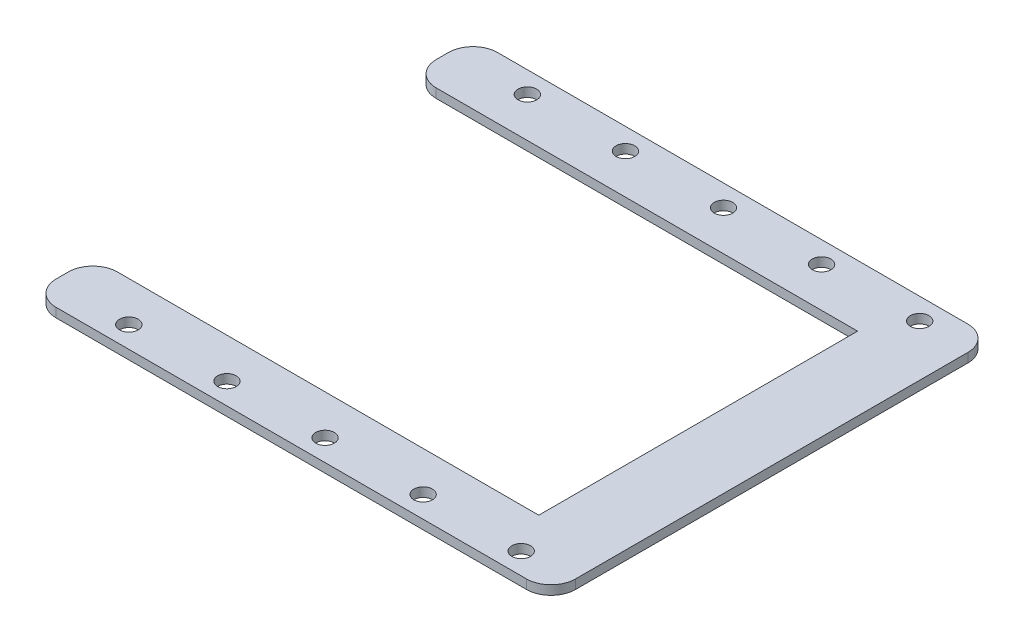
SolidWorks part; units mm, degrees
ref_plane "Front Plane" through (0, 0, 0) normal (0, 0, 1) x (1, 0, 0)
ref_plane "Top Plane" through (0, 0, 0) normal (0, 1, 0) x (1, 0, 0)
ref_plane "Right Plane" through (0, 0, 0) normal (1, 0, 0) x (0, 0, -1)
sketch "Sketch1" plane through (0, 0, 0) normal (0, 1, 0) x (1, 0, 0)
  line L0 (-76.7804, -46.0375) -> (76.7804, -46.0375) construction
  line L1 (76.7804, -57.15) -> (-76.7804, -57.15)
  line L2 (76.7804, -57.15) -> (76.7804, 57.15)
  line L3 (76.7804, 57.15) -> (-76.7804, 57.15)
  line L4 (-76.7804, -57.15) -> (-76.7804, 57.15)
  line L5 (76.7804, -57.15) -> (-76.7804, 57.15) construction
  line L6 (76.7804, 57.15) -> (-76.7804, -57.15) construction
  line L7 (57.7304, -41.275) -> (-63.1045, -41.275)
  line L8 (57.7304, -41.275) -> (57.7304, 15.875)
  line L9 (21.3279, 41.275) -> (57.7304, 41.275)
  line L10 (-63.1045, -41.275) -> (-63.1045, 41.275)
  line L11 (-76.7804, 0) -> (76.7804, 0) construction
  line L12 (21.3279, 41.275) -> (-63.1045, 41.275)
  line L13 (-76.7804, -51.5937) -> (76.7804, -51.5937) construction
  line L14 (63.5, -51.5938) -> (76.7804, -46.0375) construction
  line L15 (-63.5, -51.5938) -> (-76.7804, -46.0375) construction
  line L16 (57.7304, 41.275) -> (57.7304, 15.875)
  circle A0 centre (-63.5, -51.5938) radius 2.413
  circle A1 centre (-38.1, -51.5938) radius 2.413
  circle A2 centre (-12.7, -51.5938) radius 2.413
  circle A3 centre (12.7, -51.5938) radius 2.413
  circle A4 centre (38.1, -51.5938) radius 2.413
  circle A5 centre (63.5, -51.5938) radius 2.413
  circle A6 centre (63.5, 51.5938) radius 2.413
  circle A7 centre (38.1, 51.5938) radius 2.413
  circle A8 centre (12.7, 51.5938) radius 2.413
  circle A9 centre (-12.7, 51.5937) radius 2.413
  circle A10 centre (-38.1, 51.5937) radius 2.413
  circle A11 centre (-63.5, 51.5937) radius 2.413
  point P0 (0, 0)
  point P6 (0, 0)
  dimension "D6" = 4.826
  dimension "D8" = 25.4
  dimension "D1" = 114.3
  dimension "D2" = 153.5608
  dimension "D3" = 15.875
  dimension "D4" = 11.1125
  dimension "D5" = 5.5562
  dimension "D10" = 13.6759
  dimension "D11" = 19.05
  dimension "D7" = 6
base flange "Base-Flange1" sketch "Sketch1" thickness 2.3813 reverse thickness direction no parameters "D1"=2.3813
fillet "Fillet1" radius 6.35 4 edges at (-76.7804, -1.1906, 57.15) (-76.7804, -1.1906, -57.15) (76.7804, -1.1906, -57.15) (76.7804, -1.1906, 57.15)
sketch "Sketch7" plane through (0, -2.3813, 0) normal (0, -1, 0) x (-1, 0, 0)
  line L0 (57.7304, 57.15) -> (57.7304, -57.15)
  line L1 (-70.4304, 57.15) -> (70.4304, 57.15) construction
  line L2 (70.4304, -57.15) -> (-70.4304, -57.15) construction
  line L3 (57.7304, -57.15) -> (76.7804, -57.15)
  line L4 (76.7804, -57.15) -> (76.7804, 57.15)
  line L5 (76.7804, 57.15) -> (57.7304, 57.15)
  line L6 (76.7804, 50.8) -> (76.7804, -50.8) construction
  dimension "D1" = 0
  dimension "D2" = 19.05
extrude "Cut-Extrude2" cut sketch "Sketch7" against normal blind 2.54
fillet "Fillet2" radius 6.35 4 edges at (-57.7304, -1.1906, -57.15) (-57.7304, -1.1906, 41.275) (-57.7304, -1.1906, 57.15) (-57.7304, -1.1906, -41.275)
sketch "Bend-Lines1" plane through (0, 0, 0) normal (0, 1, 0) x (1, 0, 0)
sketch "Bounding-Box1" plane through (0, 0, 0) normal (0, 1, 0) x (1, 0, 0)
sheet metal parameters "Sheet-Metal1" thickness 2.3813 parameters "D1"=2.3813
flat pattern "Flat-Pattern1" [suppressed]
sketch "Bend-Lines2" plane through (0, 0, 0) normal (0, 1, 0) x (1, 0, 0)
sketch "Bounding-Box2" [suppressed] plane through (0, 0, 0) normal (0, 1, 0) x (1, 0, 0)
sheet metal parameters "Sheet-Metal3" thickness 2.3813 parameters "D1"=2.3813
flat pattern "Flat-Pattern1"
sketch "Bend-Lines2" plane through (0, 0, 0) normal (0, 1, 0) x (1, 0, 0)
sketch "Bounding-Box2" [suppressed] plane through (0, 0, 0) normal (0, 1, 0) x (1, 0, 0)
